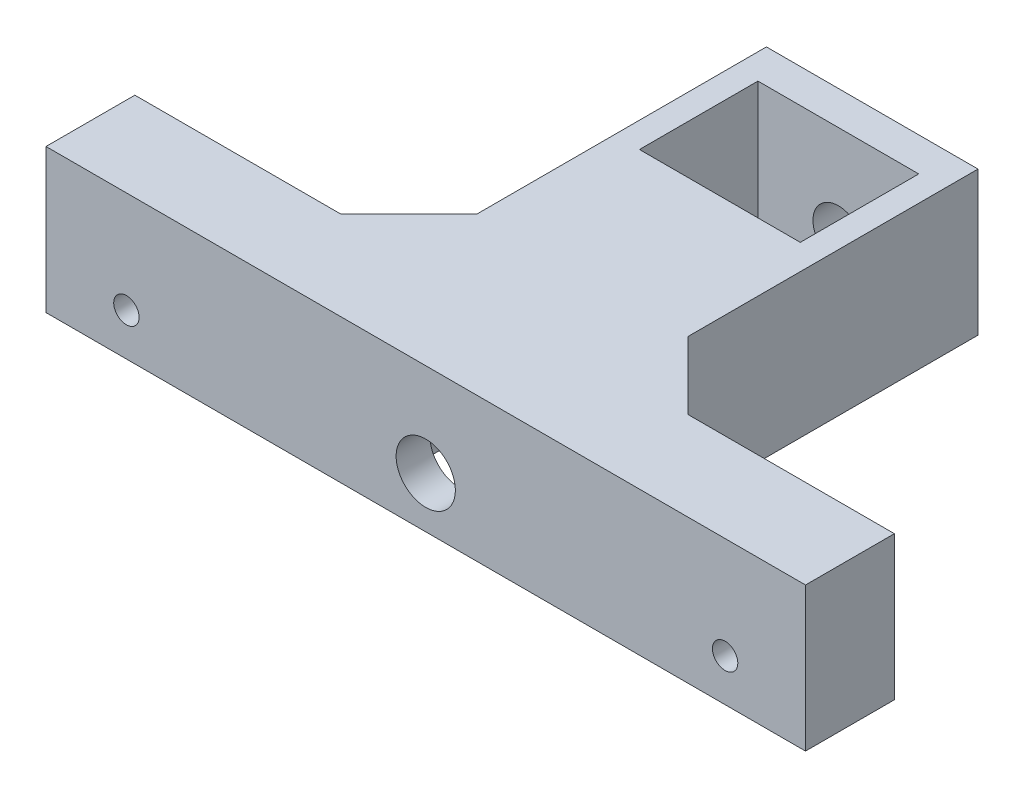
SolidWorks part; units mm, degrees
ref_plane "前视基准面" through (0, 0, 0) normal (0, 0, 1) x (1, 0, 0)
ref_plane "上视基准面" through (0, 0, 0) normal (0, 1, 0) x (1, 0, 0)
ref_plane "右视基准面" through (0, 0, 0) normal (1, 0, 0) x (0, 0, -1)
other "Configuration Table"
sketch "草图1" plane through (0, 0, 0) normal (0, 1, 0) x (1, 0, 0)
  line L6 (-30.87, 10.5) -> (-12.5, 10.5)
  line L10 (-12.5, 52.75) -> (12.5, 52.75)
  line L14 (12.5, 10.5) -> (30.87, 10.5)
  line L20 (0, 48.75) -> (0, 31.75) construction
  line L21 (-9.5, 48.75) -> (9.5, 48.75)
  line L22 (-9.5, 48.75) -> (-9.5, 34.75)
  line L23 (-9.5, 34.75) -> (9.5, 34.75)
  line L24 (9.5, 48.75) -> (9.5, 34.75)
  line L25 (-7.5, 31.75) -> (7.5, 31.75)
  line L29 (30.87, 10.5) -> (30.87, 4)
  line L30 (30.87, 4) -> (39.87, 4)
  line L31 (39.87, 4) -> (39.87, 10.5)
  line L32 (39.87, 10.5) -> (44.87, 10.5)
  line L33 (44.87, 10.5) -> (44.87, 0)
  line L34 (44.87, 0) -> (-44.87, 0)
  line L35 (-44.87, 0) -> (-44.87, 10.5)
  line L36 (-44.87, 10.5) -> (-39.87, 10.5)
  line L37 (-39.87, 10.5) -> (-39.87, 4)
  line L38 (-39.87, 4) -> (-30.87, 4)
  line L39 (-30.87, 4) -> (-30.87, 10.5)
  line L40 (0, 7.5148) -> (0, 0) construction
  line L46 (7.5, 4) -> (-7.5, 4)
  line L52 (12.5, 52.75) -> (12.5, 10.5)
  line L53 (-12.5, 52.75) -> (-12.5, 10.5)
  line L54 (-7.5, 31.75) -> (-7.5, 7.5)
  line L55 (7.5, 31.75) -> (7.5, 7.5)
  line L56 (-7.5, 7.5) -> (-7.5, 4)
  line L57 (7.5, 7.5) -> (7.5, 4)
  point P38 (0, 4)
  dimension "D3" = 9
  dimension "D4" = 18.37
  dimension "D5" = 25
  dimension "D6" = 9
  dimension "D7" = 42.25
  dimension "D8" = 3
  dimension "D9" = 3
  dimension "D10" = 18.37
  dimension "D12" = 5
  dimension "D13" = 5
  dimension "D15" = 4
  dimension "D17" = 4
  dimension "D20" = 14
  dimension "D21" = 6.5
  dimension "D22" = 3
  dimension "D23" = 6.5
  dimension "D24" = 4
  dimension "D27" = 6.5
  dimension "D28" = 4
  dimension "D30" = 5
extrude "凸台-拉伸1" add sketch "草图1" along normal blind 12
sketch "草图4" plane through (0, 0, 0) normal (0, 0, 1) x (1, 0, 0)
  line L0 (-35.37, 12) -> (-35.37, 5)
  line L1 (-44.87, 12) -> (44.87, 12) construction
  line L2 (-44.87, 12) -> (-44.87, 0) construction
  line L3 (0, 12) -> (0, 0)
  line L12 (-44.87, 0) -> (44.87, 0) construction
  line L14 (-44.87, 12) -> (44.87, 12)
  line L15 (-44.87, 12) -> (-44.87, 0)
  line L16 (-44.87, 0) -> (44.87, 0)
  line L17 (44.87, 12) -> (44.87, 0)
  circle A3 centre (-35.37, 5) radius 1.5
  circle A4 centre (35.37, 5) radius 1.5
  dimension "D1" = 3
  dimension "D2" = 7
  dimension "D3" = 9.5
extrude "切除-拉伸2" cut sketch "草图4" against normal up to next contours A3 | A4
sketch "草图5" plane through (0, 12, 0) normal (0, 1, 0) x (1, 0, 0)
  line L0 (-39.87, 10.5) -> (-30.87, 10.5)
  line L1 (-9.5, 48.75) -> (9.5, 48.75)
  line L2 (-9.5, 48.75) -> (-9.5, 34.75)
  line L3 (-9.5, 34.75) -> (9.5, 34.75)
  line L4 (9.5, 48.75) -> (9.5, 34.75)
  line L5 (30.87, 10.5) -> (39.87, 10.5)
  line L20 (44.87, 10.5) -> (39.87, 10.5)
  line L21 (39.87, 10.5) -> (39.87, 4)
  line L22 (39.87, 4) -> (30.87, 4)
  line L23 (30.87, 4) -> (30.87, 10.5)
  line L24 (30.87, 10.5) -> (12.5, 10.5)
  line L25 (-12.5, 52.75) -> (-12.5, 10.5)
  line L26 (-12.5, 52.75) -> (-12.5, 10.5)
  line L27 (12.5, 10.5) -> (12.5, 52.75)
  line L28 (12.5, 52.75) -> (-12.5, 52.75)
  line L32 (-12.5, 10.5) -> (-30.87, 10.5)
  line L33 (-30.87, 10.5) -> (-30.87, 4)
  line L34 (-30.87, 4) -> (-39.87, 4)
  line L35 (-39.87, 4) -> (-39.87, 10.5)
  line L36 (-39.87, 10.5) -> (-44.87, 10.5)
  line L37 (-44.87, 10.5) -> (-44.87, 0)
  line L38 (-44.87, 0) -> (44.87, 0)
  line L39 (44.87, 0) -> (44.87, 10.5)
  line L40 (44.87, 10.5) -> (39.87, 10.5)
  line L44 (30.87, 10.5) -> (12.5, 10.5)
  line L47 (12.5, 10.5) -> (12.5, 52.75)
  line L48 (12.5, 52.75) -> (-12.5, 52.75)
  line L52 (-12.5, 10.5) -> (-30.87, 10.5)
  line L56 (-39.87, 10.5) -> (-44.87, 10.5)
  line L57 (-44.87, 10.5) -> (-44.87, 0)
  line L58 (-44.87, 0) -> (44.87, 0)
  line L59 (44.87, 0) -> (44.87, 10.5)
  dimension "D1" = 0
extrude "凸台-拉伸2" add sketch "草图5" along normal blind 5
sketch "草图6" plane through (0, 0, -52.75) normal (0, 0, -1) x (-1, 0, 0)
  line L0 (-12.5, 0) -> (12.5, 0) construction
  circle A2 centre (0, 6) radius 3
  dimension "D1" = 6
  dimension "D2" = 6
extrude "切除-拉伸4" cut sketch "草图6" against normal up to surface (21 mm away) up to face at (0, 6, -31.75)
sketch "草图7" plane through (0, 0, 0) normal (0, 0, 1) x (1, 0, 0)
  line L0 (-44.87, 17) -> (44.87, 17) construction
  line L1 (0, 17) -> (0, 0) construction
  line L3 (-44.87, 0) -> (44.87, 0) construction
  circle A0 centre (0, 6) radius 3.5
  dimension "D1" = 7
  dimension "D2" = 6
extrude "切除-拉伸5" cut sketch "草图7" against normal up to surface (4 mm away) up to face at (0, 6, -4)
chamfer "倒角1" distance 4 angle 45 4 edges at (7.5, 6, -4) (7.5, 6, -31.75) (-7.5, 6, -31.75) (-7.5, 6, -4)
chamfer "倒角2" distance 8 angle 45 2 edges at (12.5, 8.5, -10.5) (-12.5, 8.5, -10.5)
